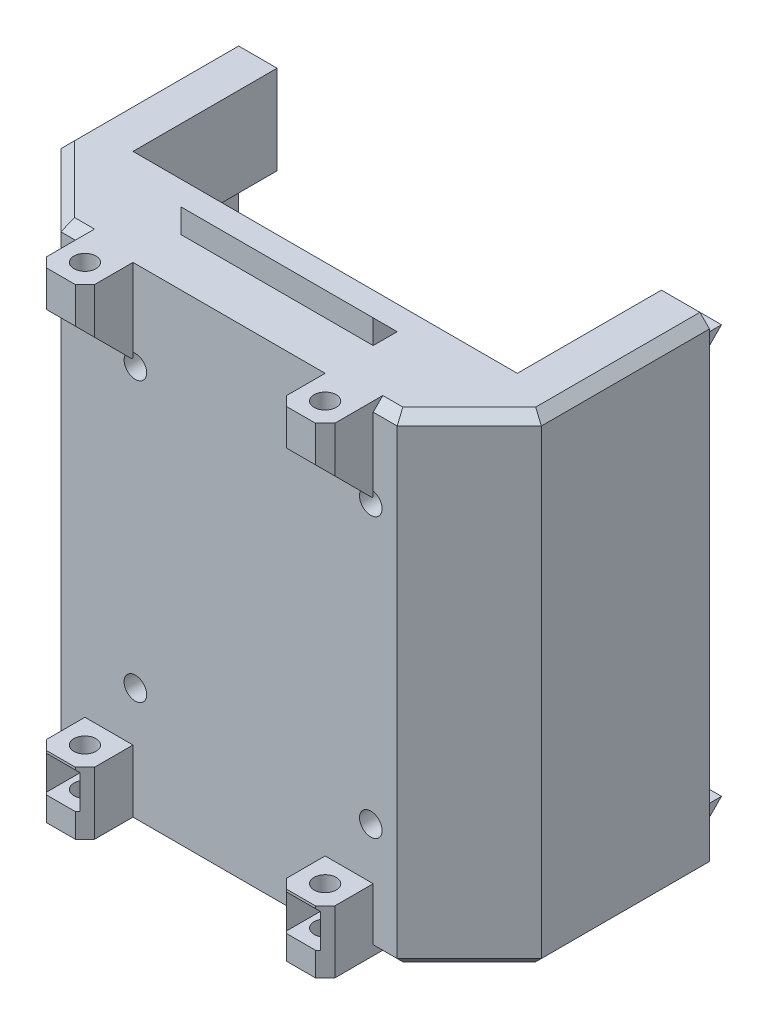
SolidWorks part; units mm, degrees
ref_plane "Front Plane" through (0, 0, 0) normal (0, 0, 1) x (1, 0, 0)
ref_plane "Top Plane" through (0, 0, 0) normal (0, 1, 0) x (1, 0, 0)
ref_plane "Right Plane" through (0, 0, 0) normal (1, 0, 0) x (0, 0, -1)
sketch "Sketch1" plane through (0, 0, 0) normal (0, 1, 0) x (1, 0, 0)
  line L0 (-50, 0) -> (50, 0)
  line L1 (-50, 0) -> (-50, 50)
  line L2 (50, 0) -> (50, 50)
  line L3 (-50, 50) -> (50, 50)
  point P4 (0, 0)
extrude "Boss-Extrude1" add sketch "Sketch1" along normal blind 100
chamfer "Chamfer1" distance 15 2 edges at (-50, 50, 0) (50, 50, 0)
ref_plane "Plane1" through (0, 100, 0) normal (0, 1, 0) x (1, 0, 0)
sketch "Sketch2" plane through (0, 100, 0) normal (0, 1, 0) x (1, 0, 0)
  line L0 (0, 0) -> (0, 20) construction
  line L1 (-40, 20) -> (40, 20)
  line L2 (-40, 20) -> (-50, 20) construction
  line L4 (-50, 50) -> (-50, 15) construction
  line L5 (40, 20) -> (50, 20) construction
  line L6 (50, 15) -> (50, 50) construction
  line L7 (-40, 20) -> (-40, 50)
  line L8 (50, 50) -> (-50, 50) construction
  line L9 (40, 20) -> (40, 50)
  line L10 (40, 50) -> (-40, 50)
  point P6 (0, 20)
  dimension "D1" = 20
  dimension "D2" = 10
extrude "Cut-Extrude1" cut sketch "Sketch2" against normal up to next
sketch "Sketch3" plane through (0, 100, 0) normal (0, 1, 0) x (1, 0, 0)
  line L0 (-20, 0) -> (20, 0) construction
  line L1 (-35, 0) -> (35, 0) construction
  line L2 (20, 0) -> (20, -10)
  line L3 (20, -10) -> (30, -10)
  line L4 (30, -10) -> (30, 0)
  line L5 (30, 0) -> (20, 0)
  line L6 (-20, 0) -> (-20, -10)
  line L7 (-20, -10) -> (-30, -10)
  line L8 (-30, -10) -> (-30, 0)
  line L9 (-30, 0) -> (-20, 0)
  circle A0 centre (-25, -5) radius 2.3
  circle A1 centre (25, -5) radius 2.3
  point P6 (0, 0)
  dimension "D5" = 4.6
  dimension "D6" = 4.6
  dimension "D1" = 10
  dimension "D2" = 10
  dimension "D3" = 40
  dimension "D4" = 10
extrude "Boss-Extrude2" add sketch "Sketch3" against normal blind 7.5
extrude "Boss-Extrude3" add sketch "Sketch3<2>" along normal blind 13 from surface starting at face at (0, 0, -27)
sketch "Sketch3<2>" plane through (0, 100, 0) normal (0, 1, 0) x (1, 0, 0) same geometry as "Sketch3"
ref_plane "Plane2" through (0, 0, 10) normal (0, 0, 1) x (1, 0, 0)
sketch "Sketch4" plane through (0, 0, 10) normal (0, 0, 1) x (1, 0, 0)
  line L0 (25, 0) -> (25, 5) construction
  line L1 (30, 0) -> (20, 0) construction
  line L2 (21.5, 5) -> (28.5, 5)
  line L3 (28.5, 5) -> (28.5, 8.5)
  line L4 (28.5, 8.5) -> (21.5, 8.5)
  line L5 (21.5, 8.5) -> (21.5, 5)
  line L6 (-25, 0) -> (-25, 5) construction
  line L7 (-20, 0) -> (-30, 0) construction
  line L8 (-28.5, 5) -> (-21.5, 5)
  line L9 (-21.5, 5) -> (-21.5, 8.5)
  line L10 (-21.5, 8.5) -> (-28.5, 8.5)
  line L11 (-28.5, 8.5) -> (-28.5, 5)
  point P7 (25, 5)
  point P16 (-25, 5)
  dimension "D1" = 5
  dimension "D2" = 7
  dimension "D3" = 3.5
  dimension "D4" = 7
extrude "Cut-Extrude2" cut sketch "Sketch4" against normal blind 9
chamfer "Chamfer2" distance 4 2 edges at (25, 8.5, 10) (-25, 8.5, 10)
chamfer "Chamfer3" distance 10 2 edges at (25, 92.5, 0) (-25, 92.5, 0)
sketch "Sketch5" plane through (0, 100, 0) normal (0, 1, 0) x (1, 0, 0)
  circle A0 centre (-25, -5) radius 3.55
  circle A1 centre (25, -5) radius 3.55
  dimension "D1" = 7.1
  dimension "D2" = 7.1
extrude "Cut-Extrude3" cut sketch "Sketch5" against normal up to next from offset 7 offset against normal yes
sketch "Sketch6" plane through (0, 100, 0) normal (0, 1, 0) x (1, 0, 0)
  line L0 (-20, 0) -> (-20, 10) construction
  line L1 (-20, 10) -> (20, 10)
  line L2 (20, 10) -> (20, 15)
  line L3 (20, 15) -> (-20, 15)
  line L4 (-20, 15) -> (-20, 10)
  dimension "D1" = 10
  dimension "D2" = 40
  dimension "D3" = 5
extrude "Boss-Extrude4" add sketch "Sketch6" along normal blind 5
chamfer "Chamfer4" distance 5 1 edges at (0, 105, -15)
extrude "Cut-Extrude4" cut sketch "Sketch6<2>" along normal blind 5 from surface starting at face at (0, 0, -12.7778)
sketch "Sketch6<2>" plane through (0, 100, 0) normal (0, 1, 0) x (1, 0, 0) same geometry as "Sketch6"
chamfer "Chamfer5" distance 4.75 1 edges at (0, 5, -15)
ref_plane "Plane3" through (0, 0, -50) normal (0, 0, -1) x (-1, 0, 0)
sketch "Sketch7" plane through (0, 0, -50) normal (0, 0, -1) x (-1, 0, 0)
  line L0 (45, 0) -> (45, 5) construction
  line L1 (40, 0) -> (50, 0) construction
  line L2 (45, 100) -> (45, 95) construction
  line L3 (40, 100) -> (50, 100) construction
  line L4 (47.5, 5) -> (42.5, 5)
  line L5 (42.5, 5) -> (42.5, 10)
  line L6 (42.5, 10) -> (47.5, 10)
  line L7 (47.5, 10) -> (47.5, 5)
  line L8 (47.5, 95) -> (42.5, 95)
  line L9 (42.5, 95) -> (42.5, 90)
  line L10 (42.5, 90) -> (47.5, 90)
  line L11 (47.5, 90) -> (47.5, 95)
  point P11 (45, 5)
  point P16 (45, 95)
  dimension "D2" = 5
  dimension "D4" = 5
  dimension "D1" = 5
  dimension "D3" = 5
  dimension "D5" = 5
  dimension "D6" = 5
extrude "Cut-Extrude5" cut sketch "Sketch7" against normal blind 5
sketch "Sketch8" plane through (0, 0, -50) normal (0, 0, -1) x (-1, 0, 0)
  line L0 (-45, 100) -> (-45, 95) construction
  line L1 (-50, 100) -> (-40, 100) construction
  line L2 (-45, 0) -> (-45, 5) construction
  line L3 (-50, 0) -> (-40, 0) construction
  line L4 (-47.5, 95) -> (-42.5, 95)
  line L5 (-42.5, 95) -> (-42.5, 90)
  line L6 (-42.5, 90) -> (-47.5, 90)
  line L7 (-47.5, 90) -> (-47.5, 95)
  line L8 (-47.5, 5) -> (-42.5, 5)
  line L9 (-42.5, 5) -> (-42.5, 10)
  line L10 (-42.5, 10) -> (-47.5, 10)
  line L11 (-47.5, 10) -> (-47.5, 5)
  point P11 (-45, 95)
  point P16 (-45, 5)
  dimension "D3" = 5
  dimension "D4" = 5
  dimension "D1" = 5
  dimension "D2" = 5
  dimension "D5" = 5
  dimension "D6" = 5
extrude "Boss-Extrude5" add sketch "Sketch8" along normal blind 5
chamfer "Chamfer6" distance 5 2 edges at (45, 5, -55) (45, 90, -55)
chamfer "Chamfer7" distance 4.75 2 edges at (-45, 90, -45) (-45, 5, -45)
chamfer "Chamfer8" distance 2 8 edges at (30, 6.5, 10) (20, 6.5, 10) (-30, 6.5, 10) (-20, 6.5, 10) (-30, 96.25, 10) (-20, 96.25, 10) (20, 96.25, 10) (30, 96.25, 10)
chamfer "Chamfer9" distance 2 12 edges at (-50, 0, -32.5) (-42.5, 0, -7.5) (-32.5, 0, 0) (32.5, 0, 0) (50, 0, -32.5) (42.5, 0, -7.5) (50, 100, -32.5) (42.5, 100, -7.5) (32.5, 100, 0) (-32.5, 100, 0) (-50, 100, -32.5) (-42.5, 100, -7.5)
ref_plane "Plane4" through (0, 0, -20) normal (0, 0, -1) x (-1, 0, 0)
sketch "Sketch9" plane through (0, 0, -20) normal (0, 0, -1) x (-1, 0, 0)
  line L0 (0, 0) -> (19.5, 0) construction
  line L2 (-29.5, 0) -> (-29.5, 81.5) construction
  line L3 (-29.5, 81.5) -> (19.5, 81.5) construction
  line L4 (19.5, 81.5) -> (19.5, 0) construction
  line L5 (-29.5, 81.5) -> (-29.5, 23.5) construction
  line L6 (-29.5, 23.5) -> (19.5, 23.5) construction
  line L7 (19.5, 23.5) -> (19.5, 81.5) construction
  line L8 (40, 0) -> (40, 100) construction
  circle A0 centre (-29.5, 81.5) radius 1.35
  circle A1 centre (19.5, 81.5) radius 1.35
  circle A2 centre (19.5, 23.5) radius 1.35
  circle A3 centre (-29.5, 23.5) radius 1.35
  point P6 (0, 0)
  dimension "D4" = 2.7
  dimension "D5" = 2.7
  dimension "D6" = 2.7
  dimension "D7" = 2.7
  dimension "D1" = 49
  dimension "D2" = 81.5
  dimension "D3" = 58
  dimension "D8" = 19.5
extrude "Cut-Extrude6" cut sketch "Sketch9" against normal up to next
sketch "Sketch10" plane through (0, 0, -50) normal (0, 0, -1) x (-1, 0, 0)
  line L0 (19.5, 81.5) -> (40, 81.5) construction
  line L1 (40, 0) -> (40, 100) construction
  line L2 (40, 81.5) -> (48, 73.5)
  line L3 (19.5, 23.5) -> (40, 23.5) construction
  line L4 (40, 23.5) -> (48, 31.5)
  line L5 (48, 31.5) -> (48, 73.5)
  line L6 (40, 81.5) -> (40, 23.5)
  line L7 (50, 98) -> (50, 2) construction
  dimension "D1" = 45
  dimension "D2" = 45
  dimension "D3" = 2
extrude "Cut-Extrude7" cut sketch "Sketch10" against normal up to surface (30 mm away) up to face at (28.15, 23.5, -20)
extrude "Cut-Extrude-Thin1" cut sketch "Sketch9<2>" along normal blind 5 from surface thin starting at face at (28.15, 23.5, 0) thin type one direction wall 1
sketch "Sketch9<2>" plane through (0, 0, -20) normal (0, 0, -1) x (-1, 0, 0) same geometry as "Sketch9"
